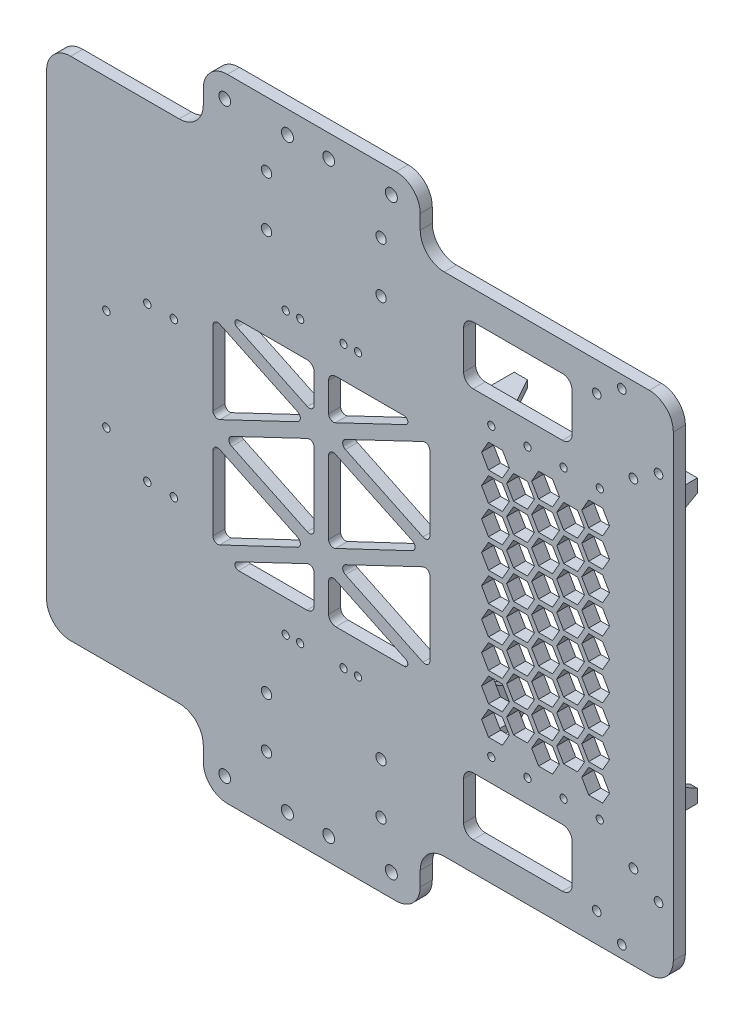
SolidWorks part; units mm, degrees
ref_plane "前视基准面" through (0, 0, 0) normal (0, 0, 1) x (1, 0, 0)
ref_plane "上视基准面" through (0, 0, 0) normal (0, 1, 0) x (1, 0, 0)
ref_plane "右视基准面" through (0, 0, 0) normal (1, 0, 0) x (0, 0, -1)
sketch "草图1" plane through (0, 0, 0) normal (0, 0, 1) x (1, 0, 0)
  line L2 (-130, 95) -> (-130, -95)
  line L3 (-120, -105) -> (-75, -105)
  line L4 (130, 95) -> (130, -95)
  line L5 (126.7518, 102.3765) -> (130, 105) construction
  line L6 (-130, -105) -> (-126.7518, -102.3765) construction
  line L9 (-65, -115) -> (-65, -121)
  line L10 (-55, -131) -> (15, -131)
  line L11 (25, -121) -> (25, -115)
  line L13 (35, -105) -> (120, -105)
  line L14 (126.7518, -102.3765) -> (130, -105) construction
  line L15 (-130, 105) -> (-126.7518, 102.3765) construction
  line L16 (-130, 0) -> (130, 0) construction
  line L17 (35, 105) -> (120, 105)
  line L18 (25, 121) -> (25, 115)
  line L19 (-55, 131) -> (15, 131)
  line L20 (-65, 115) -> (-65, 121)
  line L21 (-120, 105) -> (-75, 105)
  arc A1 (-120, -105) -> (-130, -95) centre (-120, -95) cw
  arc A3 (120, -105) -> (130, -95) centre (120, -95) ccw
  arc A8 (-65, -115) -> (-75, -105) centre (-75, -115) ccw
  arc A9 (25, -115) -> (35, -105) centre (35, -115) cw
  arc A10 (-55, -131) -> (-65, -121) centre (-55, -121) cw
  arc A11 (15, -131) -> (25, -121) centre (15, -121) ccw
  arc A12 (15, 131) -> (25, 121) centre (15, 121) cw
  arc A13 (-55, 131) -> (-65, 121) centre (-55, 121) ccw
  arc A14 (25, 115) -> (35, 105) centre (35, 115) ccw
  arc A15 (-65, 115) -> (-75, 105) centre (-75, 115) cw
  arc A16 (120, 105) -> (130, 95) centre (120, 95) cw
  arc A17 (-120, 105) -> (-130, 95) centre (-120, 95) ccw
  point P0 (0, 0)
  point P40 (25, -105)
  point P45 (25, 105)
  dimension "D2" = 10
  dimension "D3" = 65
  dimension "D4" = 10
  dimension "D5" = 105
  dimension "D7" = 10
  dimension "D8" = 10
  dimension "D10" = 10
  dimension "D12" = 10
  dimension "D13" = 105
  dimension "D18" = 90
  dimension "D19" = 6
extrude "凸台-拉伸1" add sketch "草图1" along normal blind 5
sketch "草图4" plane through (0, 0, 0) normal (0, 0, -1) x (-1, 0, 0)
  line L0 (-39, -47.5) -> (-39, -58.5)
  line L1 (-39, -58.5) -> (-50, -58.5)
  line L2 (-50, -58.5) -> (-50, -55.5)
  line L3 (-50, -55.5) -> (-42, -55.5)
  line L4 (-42, -55.5) -> (-42, -47.5)
  line L5 (-42, -47.5) -> (-39, -47.5)
  line L6 (-130, 0) -> (-25.5592, 0) construction
  line L7 (-130, -95) -> (-130, 95) construction
  line L10 (-130, -95) -> (-130, 95) construction
  dimension "D1" = 11
  dimension "D2" = 11
  dimension "D3" = 3
  dimension "D4" = 3
  dimension "D5" = 80
  dimension "D7" = 55.5
extrude "凸台-拉伸2" add sketch "草图4" along normal blind 20
sketch "草图5" plane through (0, -58.5, 0) normal (0, -1, 0) x (1, 0, 0)
  line L0 (50, -10) -> (44.5, -20)
  line L1 (50, -20) -> (50, 0) construction
  line L2 (50, -20) -> (39, -20) construction
  line L3 (44.5, -20) -> (50, -20)
  line L4 (50, -20) -> (50, -10)
  dimension "D1" = 10
  dimension "D2" = 5.5
extrude "切除-拉伸3" cut sketch "草图5" against normal blind 10
sketch "草图6" plane through (39, 0, 0) normal (-1, 0, 0) x (0, 0, 1)
  line L0 (-20, -53) -> (-10, -47.5)
  line L1 (-20, -58.5) -> (-20, -47.5) construction
  line L2 (-20, -47.5) -> (0, -47.5) construction
  line L3 (-10, -47.5) -> (-20, -47.5)
  line L4 (-20, -47.5) -> (-20, -53)
  dimension "D1" = 10
  dimension "D2" = 5.5
extrude "切除-拉伸4" cut sketch "草图6" against normal blind 10
ref_plane "基准面2" through (77, 0, 0) normal (1, 0, 0) x (0, 0, -1)
mirror "镜向1" about plane through (77, 0, 0) normal (1, 0, 0) of "凸台-拉伸2", "切除-拉伸4", "切除-拉伸3"
mirror "镜向2" about plane through (0, 0, 0) normal (0, 1, 0) of "镜向1"
sketch "草图7" plane through (0, 0, 0) normal (0, 0, -1) x (-1, 0, 0)
  line L4 (-112, -55.5) -> (-104, -55.5) construction
  line L5 (-112, 47.5) -> (-112, 55.5) construction
  line L6 (-112, 55.5) -> (-104, 55.5) construction
  line L7 (-92.013, 36) -> (-94.8997, 41)
  line L8 (-94.8997, 41) -> (-100.6732, 41)
  line L9 (-100.6732, 41) -> (-103.56, 36)
  line L10 (-103.56, 36) -> (-100.6732, 31)
  line L11 (-100.6732, 31) -> (-94.8997, 31)
  line L12 (-94.8997, 31) -> (-92.013, 36)
  line L13 (-77.0019, 36) -> (-97.7865, 36) construction
  line L14 (-74.1151, 31) -> (-71.2284, 36)
  line L15 (-71.2284, 36) -> (-74.1151, 41)
  line L16 (-74.1151, 41) -> (-79.8886, 41)
  line L17 (-79.8886, 41) -> (-82.7754, 36)
  line L18 (-82.7754, 36) -> (-79.8886, 31)
  line L19 (-79.8886, 31) -> (-74.1151, 31)
  line L20 (-92.013, 24) -> (-94.8997, 29)
  line L21 (-93.1677, 30) -> (-90.2809, 25)
  line L22 (-90.2809, 25) -> (-84.5074, 25)
  line L23 (-84.5074, 25) -> (-81.6207, 30)
  line L24 (-81.6207, 30) -> (-84.5074, 35)
  line L25 (-84.5074, 35) -> (-90.2809, 35)
  line L26 (-90.2809, 35) -> (-93.1677, 30)
  line L27 (-84.5074, 37) -> (-81.6207, 42)
  line L28 (-81.6207, 42) -> (-84.5074, 47)
  line L29 (-84.5074, 47) -> (-90.2809, 47)
  line L30 (-90.2809, 47) -> (-93.1677, 42)
  line L31 (-93.1677, 42) -> (-90.2809, 37)
  line L32 (-90.2809, 37) -> (-84.5074, 37)
  line L33 (-79.8886, 43) -> (-74.1151, 43)
  line L34 (-74.1151, 43) -> (-71.2284, 48)
  line L35 (-71.2284, 48) -> (-74.1151, 53)
  line L36 (-74.1151, 53) -> (-79.8886, 53)
  line L37 (-79.8886, 53) -> (-82.7754, 48)
  line L38 (-82.7754, 48) -> (-79.8886, 43)
  line L39 (-94.8997, 43) -> (-92.013, 48)
  line L40 (-92.013, 48) -> (-94.8997, 53)
  line L41 (-94.8997, 53) -> (-100.6732, 53)
  line L42 (-100.6732, 53) -> (-103.56, 48)
  line L43 (-103.56, 48) -> (-100.6732, 43)
  line L44 (-100.6732, 43) -> (-94.8997, 43)
  line L45 (-72.3831, 42) -> (-69.4963, 37)
  line L46 (-69.4963, 37) -> (-63.7228, 37)
  line L47 (-63.7228, 37) -> (-60.8361, 42)
  line L48 (-60.8361, 42) -> (-63.7228, 47)
  line L49 (-63.7228, 47) -> (-69.4963, 47)
  line L50 (-69.4963, 47) -> (-72.3831, 42)
  line L51 (-94.8997, 29) -> (-100.6732, 29)
  line L52 (-100.6732, 29) -> (-103.56, 24)
  line L53 (-103.56, 24) -> (-100.6732, 19)
  line L54 (-100.6732, 19) -> (-94.8997, 19)
  line L55 (-94.8997, 19) -> (-92.013, 24)
  line L56 (-93.1677, 18) -> (-90.2809, 13)
  line L57 (-90.2809, 13) -> (-84.5074, 13)
  line L58 (-84.5074, 13) -> (-81.6207, 18)
  line L59 (-81.6207, 18) -> (-84.5074, 23)
  line L60 (-84.5074, 23) -> (-90.2809, 23)
  line L61 (-90.2809, 23) -> (-93.1677, 18)
  line L62 (-74.1151, 19) -> (-71.2284, 24)
  line L63 (-71.2284, 24) -> (-74.1151, 29)
  line L64 (-74.1151, 29) -> (-79.8886, 29)
  line L65 (-79.8886, 29) -> (-82.7754, 24)
  line L66 (-82.7754, 24) -> (-79.8886, 19)
  line L67 (-79.8886, 19) -> (-74.1151, 19)
  line L68 (-72.3831, 30) -> (-69.4963, 25)
  line L69 (-69.4963, 25) -> (-63.7228, 25)
  line L70 (-63.7228, 25) -> (-60.8361, 30)
  line L71 (-60.8361, 30) -> (-63.7228, 35)
  line L72 (-63.7228, 35) -> (-69.4963, 35)
  line L73 (-69.4963, 35) -> (-72.3831, 30)
  line L74 (-92.013, 12) -> (-94.8997, 17)
  line L75 (-94.8997, 17) -> (-100.6732, 17)
  line L76 (-100.6732, 17) -> (-103.56, 12)
  line L77 (-103.56, 12) -> (-100.6732, 7)
  line L78 (-100.6732, 7) -> (-94.8997, 7)
  line L79 (-94.8997, 7) -> (-92.013, 12)
  line L80 (-93.1677, 6) -> (-90.2809, 1)
  line L81 (-90.2809, 1) -> (-84.5074, 1)
  line L82 (-84.5074, 1) -> (-81.6207, 6)
  line L83 (-81.6207, 6) -> (-84.5074, 11)
  line L84 (-84.5074, 11) -> (-90.2809, 11)
  line L85 (-90.2809, 11) -> (-93.1677, 6)
  line L86 (-74.1151, 7) -> (-71.2284, 12)
  line L87 (-71.2284, 12) -> (-74.1151, 17)
  line L88 (-74.1151, 17) -> (-79.8886, 17)
  line L89 (-79.8886, 17) -> (-82.7754, 12)
  line L90 (-82.7754, 12) -> (-79.8886, 7)
  line L91 (-79.8886, 7) -> (-74.1151, 7)
  line L92 (-72.3831, 18) -> (-69.4963, 13)
  line L93 (-69.4963, 13) -> (-63.7228, 13)
  line L94 (-63.7228, 13) -> (-60.8361, 18)
  line L95 (-60.8361, 18) -> (-63.7228, 23)
  line L96 (-63.7228, 23) -> (-69.4963, 23)
  line L97 (-69.4963, 23) -> (-72.3831, 18)
  line L98 (-92.013, 0) -> (-94.8997, 5)
  line L99 (-94.8997, 5) -> (-100.6732, 5)
  line L100 (-100.6732, 5) -> (-103.56, 0)
  line L101 (-103.56, 0) -> (-100.6732, -5)
  line L102 (-100.6732, -5) -> (-94.8997, -5)
  line L103 (-94.8997, -5) -> (-92.013, 0)
  line L104 (-93.1677, -6) -> (-90.2809, -11)
  line L105 (-90.2809, -11) -> (-84.5074, -11)
  line L106 (-84.5074, -11) -> (-81.6207, -6)
  line L107 (-81.6207, -6) -> (-84.5074, -1)
  line L108 (-84.5074, -1) -> (-90.2809, -1)
  line L109 (-90.2809, -1) -> (-93.1677, -6)
  line L110 (-74.1151, -5) -> (-71.2284, 0)
  line L111 (-71.2284, 0) -> (-74.1151, 5)
  line L112 (-74.1151, 5) -> (-79.8886, 5)
  line L113 (-79.8886, 5) -> (-82.7754, 0)
  line L114 (-82.7754, 0) -> (-79.8886, -5)
  line L115 (-79.8886, -5) -> (-74.1151, -5)
  line L116 (-72.3831, 6) -> (-69.4963, 1)
  line L117 (-69.4963, 1) -> (-63.7228, 1)
  line L118 (-63.7228, 1) -> (-60.8361, 6)
  line L119 (-60.8361, 6) -> (-63.7228, 11)
  line L120 (-63.7228, 11) -> (-69.4963, 11)
  line L121 (-69.4963, 11) -> (-72.3831, 6)
  line L122 (-92.013, -12) -> (-94.8997, -7)
  line L123 (-94.8997, -7) -> (-100.6732, -7)
  line L124 (-100.6732, -7) -> (-103.56, -12)
  line L125 (-103.56, -12) -> (-100.6732, -17)
  line L126 (-100.6732, -17) -> (-94.8997, -17)
  line L127 (-94.8997, -17) -> (-92.013, -12)
  line L128 (-93.1677, -18) -> (-90.2809, -23)
  line L129 (-90.2809, -23) -> (-84.5074, -23)
  line L130 (-84.5074, -23) -> (-81.6207, -18)
  line L131 (-81.6207, -18) -> (-84.5074, -13)
  line L132 (-84.5074, -13) -> (-90.2809, -13)
  line L133 (-90.2809, -13) -> (-93.1677, -18)
  line L134 (-74.1151, -17) -> (-71.2284, -12)
  line L135 (-71.2284, -12) -> (-74.1151, -7)
  line L136 (-74.1151, -7) -> (-79.8886, -7)
  line L137 (-79.8886, -7) -> (-82.7754, -12)
  line L138 (-82.7754, -12) -> (-79.8886, -17)
  line L139 (-79.8886, -17) -> (-74.1151, -17)
  line L140 (-72.3831, -6) -> (-69.4963, -11)
  line L141 (-69.4963, -11) -> (-63.7228, -11)
  line L142 (-63.7228, -11) -> (-60.8361, -6)
  line L143 (-60.8361, -6) -> (-63.7228, -1)
  line L144 (-63.7228, -1) -> (-69.4963, -1)
  line L145 (-69.4963, -1) -> (-72.3831, -6)
  line L146 (-92.013, -24) -> (-94.8997, -19)
  line L147 (-94.8997, -19) -> (-100.6732, -19)
  line L148 (-100.6732, -19) -> (-103.56, -24)
  line L149 (-103.56, -24) -> (-100.6732, -29)
  line L150 (-100.6732, -29) -> (-94.8997, -29)
  line L151 (-94.8997, -29) -> (-92.013, -24)
  line L152 (-93.1677, -30) -> (-90.2809, -35)
  line L153 (-90.2809, -35) -> (-84.5074, -35)
  line L154 (-84.5074, -35) -> (-81.6207, -30)
  line L155 (-81.6207, -30) -> (-84.5074, -25)
  line L156 (-84.5074, -25) -> (-90.2809, -25)
  line L157 (-90.2809, -25) -> (-93.1677, -30)
  line L158 (-74.1151, -29) -> (-71.2284, -24)
  line L159 (-71.2284, -24) -> (-74.1151, -19)
  line L160 (-74.1151, -19) -> (-79.8886, -19)
  line L161 (-79.8886, -19) -> (-82.7754, -24)
  line L162 (-82.7754, -24) -> (-79.8886, -29)
  line L163 (-79.8886, -29) -> (-74.1151, -29)
  line L164 (-72.3831, -18) -> (-69.4963, -23)
  line L165 (-69.4963, -23) -> (-63.7228, -23)
  line L166 (-63.7228, -23) -> (-60.8361, -18)
  line L167 (-60.8361, -18) -> (-63.7228, -13)
  line L168 (-63.7228, -13) -> (-69.4963, -13)
  line L169 (-69.4963, -13) -> (-72.3831, -18)
  line L170 (-92.013, -36) -> (-94.8997, -31)
  line L171 (-94.8997, -31) -> (-100.6732, -31)
  line L172 (-100.6732, -31) -> (-103.56, -36)
  line L173 (-103.56, -36) -> (-100.6732, -41)
  line L174 (-100.6732, -41) -> (-94.8997, -41)
  line L175 (-94.8997, -41) -> (-92.013, -36)
  line L176 (-93.1677, -42) -> (-90.2809, -47)
  line L177 (-90.2809, -47) -> (-84.5074, -47)
  line L178 (-84.5074, -47) -> (-81.6207, -42)
  line L179 (-81.6207, -42) -> (-84.5074, -37)
  line L180 (-84.5074, -37) -> (-90.2809, -37)
  line L181 (-90.2809, -37) -> (-93.1677, -42)
  line L182 (-74.1151, -41) -> (-71.2284, -36)
  line L183 (-71.2284, -36) -> (-74.1151, -31)
  line L184 (-74.1151, -31) -> (-79.8886, -31)
  line L185 (-79.8886, -31) -> (-82.7754, -36)
  line L186 (-82.7754, -36) -> (-79.8886, -41)
  line L187 (-79.8886, -41) -> (-74.1151, -41)
  line L188 (-72.3831, -30) -> (-69.4963, -35)
  line L189 (-69.4963, -35) -> (-63.7228, -35)
  line L190 (-63.7228, -35) -> (-60.8361, -30)
  line L191 (-60.8361, -30) -> (-63.7228, -25)
  line L192 (-63.7228, -25) -> (-69.4963, -25)
  line L193 (-69.4963, -25) -> (-72.3831, -30)
  line L194 (-92.013, -48) -> (-94.8997, -43)
  line L195 (-94.8997, -43) -> (-100.6732, -43)
  line L196 (-100.6732, -43) -> (-103.56, -48)
  line L197 (-103.56, -48) -> (-100.6732, -53)
  line L198 (-100.6732, -53) -> (-94.8997, -53)
  line L199 (-94.8997, -53) -> (-92.013, -48)
  line L206 (-74.1151, -53) -> (-71.2284, -48)
  line L207 (-71.2284, -48) -> (-74.1151, -43)
  line L208 (-74.1151, -43) -> (-79.8886, -43)
  line L209 (-79.8886, -43) -> (-82.7754, -48)
  line L210 (-82.7754, -48) -> (-79.8886, -53)
  line L211 (-79.8886, -53) -> (-74.1151, -53)
  line L212 (-72.3831, -42) -> (-69.4963, -47)
  line L213 (-69.4963, -47) -> (-63.7228, -47)
  line L214 (-63.7228, -47) -> (-60.8361, -42)
  line L215 (-60.8361, -42) -> (-63.7228, -37)
  line L216 (-63.7228, -37) -> (-69.4963, -37)
  line L217 (-69.4963, -37) -> (-72.3831, -42)
  line L218 (-61.9908, 36) -> (-59.104, 31)
  line L219 (-61.9908, 48) -> (-59.104, 43)
  line L220 (-59.104, 43) -> (-53.3305, 43)
  line L221 (-53.3305, 43) -> (-50.4438, 48)
  line L222 (-50.4438, 48) -> (-53.3305, 53)
  line L223 (-53.3305, 53) -> (-59.104, 53)
  line L224 (-59.104, 53) -> (-61.9908, 48)
  line L225 (-59.104, 31) -> (-53.3305, 31)
  line L226 (-53.3305, 31) -> (-50.4438, 36)
  line L227 (-50.4438, 36) -> (-53.3305, 41)
  line L228 (-53.3305, 41) -> (-59.104, 41)
  line L229 (-59.104, 41) -> (-61.9908, 36)
  line L230 (-61.9908, 24) -> (-59.104, 19)
  line L231 (-59.104, 19) -> (-53.3305, 19)
  line L232 (-53.3305, 19) -> (-50.4438, 24)
  line L233 (-50.4438, 24) -> (-53.3305, 29)
  line L234 (-53.3305, 29) -> (-59.104, 29)
  line L235 (-59.104, 29) -> (-61.9908, 24)
  line L236 (-61.9908, 12) -> (-59.104, 7)
  line L237 (-59.104, 7) -> (-53.3305, 7)
  line L238 (-53.3305, 7) -> (-50.4438, 12)
  line L239 (-50.4438, 12) -> (-53.3305, 17)
  line L240 (-53.3305, 17) -> (-59.104, 17)
  line L241 (-59.104, 17) -> (-61.9908, 12)
  line L242 (-61.9908, 0) -> (-59.104, -5)
  line L243 (-59.104, -5) -> (-53.3305, -5)
  line L244 (-53.3305, -5) -> (-50.4438, 0)
  line L245 (-50.4438, 0) -> (-53.3305, 5)
  line L246 (-53.3305, 5) -> (-59.104, 5)
  line L247 (-59.104, 5) -> (-61.9908, 0)
  line L248 (-61.9908, -12) -> (-59.104, -17)
  line L249 (-59.104, -17) -> (-53.3305, -17)
  line L250 (-53.3305, -17) -> (-50.4438, -12)
  line L251 (-50.4438, -12) -> (-53.3305, -7)
  line L252 (-53.3305, -7) -> (-59.104, -7)
  line L253 (-59.104, -7) -> (-61.9908, -12)
  line L254 (-61.9908, -24) -> (-59.104, -29)
  line L255 (-59.104, -29) -> (-53.3305, -29)
  line L256 (-53.3305, -29) -> (-50.4438, -24)
  line L257 (-50.4438, -24) -> (-53.3305, -19)
  line L258 (-53.3305, -19) -> (-59.104, -19)
  line L259 (-59.104, -19) -> (-61.9908, -24)
  line L260 (-61.9908, -36) -> (-59.104, -41)
  line L261 (-59.104, -41) -> (-53.3305, -41)
  line L262 (-53.3305, -41) -> (-50.4438, -36)
  line L263 (-50.4438, -36) -> (-53.3305, -31)
  line L264 (-53.3305, -31) -> (-59.104, -31)
  line L265 (-59.104, -31) -> (-61.9908, -36)
  line L266 (-61.9908, -48) -> (-59.104, -53)
  line L267 (-59.104, -53) -> (-53.3305, -53)
  line L268 (-53.3305, -53) -> (-50.4438, -48)
  line L269 (-50.4438, -48) -> (-53.3305, -43)
  line L270 (-53.3305, -43) -> (-59.104, -43)
  line L271 (-59.104, -43) -> (-61.9908, -48)
  line L272 (-93.1677, -54) -> (-90.2809, -59) [skipped]
  line L273 (-90.2809, -59) -> (-84.5074, -59) [skipped]
  line L274 (-84.5074, -59) -> (-81.6207, -54) [skipped]
  line L275 (-81.6207, -54) -> (-84.5074, -49) [skipped]
  line L276 (-84.5074, -49) -> (-90.2809, -49) [skipped]
  line L277 (-90.2809, -49) -> (-93.1677, -54) [skipped]
  circle A0 centre (-97.7865, 36) radius 5 construction
  circle A1 centre (-77.0019, 36) radius 5 construction
  circle A2 centre (-87.3942, 30) radius 5 construction
  circle A3 centre (-87.3942, 42) radius 5 construction
  circle A4 centre (-77.0019, 48) radius 5 construction
  circle A5 centre (-97.7865, 48) radius 5 construction
  circle A6 centre (-66.6096, 42) radius 5 construction
  circle A7 centre (-56.2173, 48) radius 5 construction
  point P4 (-87.3942, 37)
  dimension "D1" = 2
  dimension "D3" = 10
  dimension "D4" = 10
  dimension "D5" = 2
  dimension "D7" = 10
  dimension "D11" = 10
  dimension "D14" = 10
  dimension "D15" = 10
  dimension "D20" = 10
  dimension "D2" = 2
  dimension "D6" = 2
  dimension "D8" = 2
  dimension "D9" = 2
  dimension "D10" = 2
  dimension "D12" = 2
  dimension "D13" = 2
  dimension "D16" = 2
  dimension "D17" = 2
  dimension "D19" = 2
  dimension "D21" = 9
  dimension "D22" = 2.5
  dimension "D23" = 2.5
  dimension "D24" = 8.44
  dimension "D18" = 8
extrude "切除-拉伸5" cut sketch "草图7" against normal blind 5
sketch "草图8" plane through (0, 0, 0) normal (0, 0, -1) x (-1, 0, 0)
  line L0 (-75.3677, 120) -> (-75.3677, -120)
  line L1 (-100.0285, 77.2863) -> (-100.0285, -77.2863)
  line L2 (-100.0285, 77.2863) -> (-75.3677, 120)
  line L3 (-100.0285, -77.2863) -> (-75.3677, -120)
  line L4 (-37.1297, 0) -> (-146.8562, 0) construction
  dimension "D1" = 30
  dimension "D2" = 30
  dimension "D3" = 120
  dimension "D4" = 120
sketch "草图9" plane through (0, 0, 0) normal (0, 0, -1) x (-1, 0, 0)
  line L0 (148.8518, 0) -> (-37.1297, 0) construction
  line L1 (-29, 41) -> (-29, 4)
  line L2 (-25, -45) -> (13, -45)
  line L3 (61, -41) -> (61, -4)
  line L4 (57, 45) -> (19, 45)
  line L14 (-29, 41) -> (9.8049, 22.5)
  line L15 (57, 0) -> (19, -18.1163)
  line L16 (130, 95) -> (130, -95) construction
  line L17 (63, 93) -> (118, 93)
  line L18 (63, 93) -> (63, 66)
  line L19 (63, 66) -> (118, 66)
  line L20 (118, 93) -> (118, 66)
  line L21 (75, 105) -> (120, 105) construction
  line L22 (63, -66) -> (118, -66)
  line L23 (118, -93) -> (118, -66)
  line L24 (63, -93) -> (118, -93)
  line L25 (63, -93) -> (63, -66)
  line L26 (-120, 105) -> (-35, 105) construction
  line L27 (-43, 93) -> (-88, 93)
  line L28 (-43, 93) -> (-43, 69)
  line L29 (-43, 69) -> (-88, 69)
  line L30 (-88, 93) -> (-88, 69)
  line L31 (-130, -95) -> (-130, 95) construction
  line L32 (-43, -69) -> (-88, -69)
  line L33 (-88, -93) -> (-88, -69)
  line L34 (-43, -93) -> (-88, -93)
  line L35 (-43, -93) -> (-43, -69)
  line L36 (-25, 45) -> (13, 26.8837)
  line L37 (-25, -45) -> (13, -26.8837)
  line L38 (61, 41) -> (22.0746, 22.5575)
  line L39 (-25.5359, 0) -> (13, -18.258)
  line L40 (57, 45) -> (19, 26.8837)
  line L41 (57, -45) -> (19, -26.8837)
  line L42 (16, 61.4977) -> (16, -60.5731) construction
  line L43 (13, 45) -> (13, 26.8837)
  line L44 (19, 45) -> (19, 26.8837)
  line L45 (13, 18.258) -> (13, -18.258)
  line L46 (9.8049, 22.5) -> (-29, 4)
  line L47 (19, 18.1163) -> (57, 0)
  line L48 (22.0746, 22.5575) -> (61, 4)
  line L49 (13, 18.258) -> (-25.5359, 0)
  line L50 (19, 18.1163) -> (19, -18.1163)
  line L51 (22.0746, -22.5575) -> (61, -41)
  line L52 (9.8049, -22.5) -> (-29, -41)
  line L53 (9.8049, -22.5) -> (-29, -4)
  line L54 (22.0746, -22.5575) -> (61, -4)
  line L55 (13, -26.8837) -> (13, -45)
  line L56 (19, -26.8837) -> (19, -45)
  line L57 (13, 45) -> (-25, 45)
  line L58 (-29, -4) -> (-29, -41)
  line L59 (19, -45) -> (57, -45)
  line L60 (61, 4) -> (61, 41)
  line L61 (-44, 41) -> (-44, -37.8122) construction
  dimension "D1" = 45
  dimension "D2" = 45
  dimension "D3" = 15
  dimension "D4" = 90
  dimension "D5" = 1
  dimension "D7" = 12
  dimension "D8" = 12
  dimension "D9" = 27
  dimension "D10" = 55
  dimension "D11" = 12
  dimension "D12" = 45
  dimension "D13" = 42
  dimension "D14" = 24
  dimension "D21" = 4
  dimension "D22" = 4
  dimension "D23" = 4
  dimension "D24" = 4
  dimension "D26" = 4
  dimension "D27" = 3
  dimension "D28" = 45
extrude "切除-拉伸6" cut sketch "草图9" against normal blind 5 contours L27 L30 L29 L28 | L34 L35 L32 L33 | L4 L44 L40 | L48 L60 L38 | L47 L50 L15 | L54 L51 L3 | L56 L59 L41 | L55 L37 L2 | L53 L58 L52 | L45 L49 L39 | L46 L14 L1 | L43 L57 L36 | L57 L36 L43 region at (16.065, 22.5, 0) region at (-0.3333, -38.9612, 0) region at (-48.0249, -22.5192, 0) region at (-31.6667, 38.9612, 0) region at (-31.6667, 0, 0) region at (65.5, 81, 0) region at (65.5, -81, 0) region at (-0.3333, 38.9612, 0) region at (-48.0249, 22.5192, 0) region at (-0.1547, 0, 0) region at (-31.6667, -38.9612, 0) region at (16.065, -22.5, 0)
fillet "圆角1" radius 4 8 edges at (43, -93, 2.5) (88, -69, 2.5) (43, -69, 2.5) (88, -93, 2.5) (88, 69, 2.5) (43, 69, 2.5) (43, 93, 2.5) (88, 93, 2.5)
fillet "圆角2" radius 1.5 4 edges at (25, -45, 2.5) (-57, -45, 2.5) (25, 45, 2.5) (-57, 45, 2.5)
fillet "圆角3" radius 2 22 edges at (29, -4, 2.5) (29, 4, 2.5) (-13, -18.258, 2.5) (-61, -41, 2.5) (-61, 4, 2.5) (-13, -26.8837, 2.5) (-13, 18.258, 2.5) (-61, -4, 2.5) (-22.0746, -22.5575, 2.5) (25.5359, 0, 2.5) (-22.0746, 22.5575, 2.5) (-61, 41, 2.5) (-19, 26.8837, 2.5) (-19, -26.8837, 2.5) (-19, -18.1163, 2.5) (29, -41, 2.5) (29, 41, 2.5) (-57, 0, 2.5) (-9.8049, -22.5, 2.5) (-13, 26.8837, 2.5) (-9.8049, 22.5, 2.5) (-19, 18.1163, 2.5)
fillet "圆角4" radius 3 4 edges at (-13, -45, 2.5) (-13, 45, 2.5) (-19, -45, 2.5) (-19, 45, 2.5)
sketch "草图10" plane through (0, 0, 0) normal (0, 0, -1) x (-1, 0, 0)
  line L0 (-37.1297, 0) -> (-146.8562, 0) construction
  line L1 (-37.1297, 0) -> (-146.8562, 0) construction
  circle A0 centre (-123.8743, 76.9597) radius 1.8 construction
  circle A1 centre (-113.4687, 70.0334) radius 1.8 construction
  circle A2 centre (-108.6364, 99.852) radius 1.8 construction
  circle A3 centre (-98.2308, 92.9256) radius 1.8 construction
  circle A4 centre (105.2101, 21) radius 1.55 construction
  circle A5 centre (88.2101, 32) radius 1.55 construction
  circle A6 centre (77.2101, 32) radius 1.55 construction
  circle A7 centre (-8.75, 83.1665) radius 2.15 construction
  circle A8 centre (38.75, 83.1665) radius 2.15 construction
  circle A9 centre (38.75, 104.1665) radius 2.15 construction
  circle A10 centre (-8.75, 104.1665) radius 2.15 construction
  circle A11 centre (-13.0267, 121.679) radius 2.5 construction
  circle A12 centre (56.0941, 121.679) radius 2.45 construction
  circle A13 centre (30.0941, 121.679) radius 2.5 construction
  circle A14 centre (12.9733, 121.679) radius 2.45 construction
  circle A15 centre (-123.8743, 76.9597) radius 1.8
  circle A16 centre (-113.4687, 70.0334) radius 1.8
  circle A17 centre (-108.6364, 99.852) radius 1.8
  circle A18 centre (-98.2308, 92.9256) radius 1.8
  circle A19 centre (105.2101, 21) radius 1.55
  circle A20 centre (88.2101, 32) radius 1.55
  circle A21 centre (77.2101, 32) radius 1.55
  circle A26 centre (-13.0267, 121.679) radius 2.5
  circle A27 centre (56.0941, 121.679) radius 2.45
  circle A28 centre (30.0941, 121.679) radius 2.5
  circle A29 centre (12.9733, 121.679) radius 2.45
  circle A30 centre (12.9733, -121.679) radius 2.45
  circle A31 centre (30.0941, -121.679) radius 2.5
  circle A32 centre (56.0941, -121.679) radius 2.45
  circle A33 centre (-13.0267, -121.679) radius 2.5
  circle A38 centre (77.2101, -32) radius 1.55
  circle A39 centre (88.2101, -32) radius 1.55
  circle A40 centre (105.2101, -21) radius 1.55
  circle A41 centre (-98.2308, -92.9256) radius 1.8
  circle A42 centre (-108.6364, -99.852) radius 1.8
  circle A43 centre (-113.4687, -70.0334) radius 1.8
  circle A44 centre (-123.8743, -76.9597) radius 1.8
  circle A45 centre (-99.5, 59.5) radius 1.5 construction
  circle A46 centre (-84.5, 59.5) radius 1.5 construction
  circle A47 centre (-69.5, 59.5) radius 1.5 construction
  circle A48 centre (-54.5, 59.5) radius 1.5 construction
  circle A49 centre (0.8061, 58.25) radius 1.5 construction
  circle A50 centre (6.8061, 58.25) radius 1.5 construction
  circle A51 centre (24.8061, 58.25) radius 1.5 construction
  circle A52 centre (30.8061, 58.25) radius 1.5 construction
  circle A53 centre (-99.5, 59.5) radius 1.5
  circle A54 centre (-84.5, 59.5) radius 1.5
  circle A55 centre (-69.5, 59.5) radius 1.5
  circle A56 centre (-54.5, 59.5) radius 1.5
  circle A57 centre (0.8061, 58.25) radius 1.5
  circle A58 centre (6.8061, 58.25) radius 1.5
  circle A59 centre (24.8061, 58.25) radius 1.5
  circle A60 centre (30.8061, 58.25) radius 1.5
  circle A61 centre (30.8061, -58.25) radius 1.5
  circle A62 centre (24.8061, -58.25) radius 1.5
  circle A63 centre (6.8061, -58.25) radius 1.5
  circle A64 centre (0.8061, -58.25) radius 1.5
  circle A65 centre (-54.5, -59.5) radius 1.5
  circle A66 centre (-69.5, -59.5) radius 1.5
  circle A67 centre (-84.5, -59.5) radius 1.5
  circle A68 centre (-99.5, -59.5) radius 1.5
  circle A81 centre (-8.75, 83.1665) radius 2.15
  circle A82 centre (38.75, 83.1665) radius 2.15
  circle A83 centre (38.75, 104.1665) radius 2.15
  circle A84 centre (-8.75, 104.1665) radius 2.15
  circle A85 centre (-8.75, -104.1665) radius 2.15
  circle A86 centre (38.75, -104.1665) radius 2.15
  circle A87 centre (38.75, -83.1665) radius 2.15
  circle A88 centre (-8.75, -83.1665) radius 2.15
extrude "切除-拉伸7" cut sketch "草图10" against normal through all
equation "\"45、\"=43.7672"
